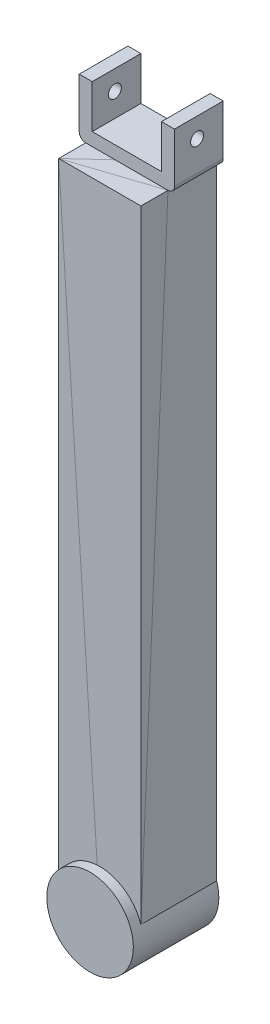
SolidWorks part; units mm, degrees
ref_plane "Front Plane" through (0, 0, 0) normal (0, 0, 1) x (1, 0, 0)
ref_plane "Top Plane" through (0, 0, 0) normal (0, 1, 0) x (1, 0, 0)
ref_plane "Right Plane" through (0, 0, 0) normal (1, 0, 0) x (0, 0, -1)
sketch "Sketch1" plane through (0, 0, 0) normal (0, 1, 0) x (1, 0, 0)
  line L1 (-19, 17.5) -> (19, 17.5)
  line L2 (-19, 17.5) -> (-19, -17.5)
  line L3 (-19, -17.5) -> (19, -17.5)
  line L4 (19, 17.5) -> (19, -17.5)
  line L5 (-19, 17.5) -> (19, -17.5) construction
  line L6 (-19, -17.5) -> (19, 17.5) construction
  point P0 (0, 0)
  dimension "D1" = 35
  dimension "D2" = 38
extrude "Boss-Extrude1" add sketch "Sketch1" against normal blind 295
sketch "Sketch2" plane through (0, 0, 0) normal (0, 0, 1) x (1, 0, 0)
  line L0 (-19, 0) -> (19, 0)
  line L1 (22, 3) -> (22, 26)
  line L2 (-22, 3) -> (-22, 26)
  line L3 (16, 6) -> (16, 26)
  line L4 (-16, 6) -> (16, 6)
  line L5 (-16, 6) -> (-16, 26)
  line L6 (-16, 26) -> (-22, 26)
  line L7 (16, 26) -> (22, 26)
  line L8 (-22, 0) -> (22, 0) construction
  line L9 (-22, 0) -> (-22, 26) construction
  line L10 (22, 0) -> (22, 26) construction
  arc A0 (-19, 0) -> (-22, 3) centre (-19, 3) cw
  arc A1 (19, 0) -> (22, 3) centre (19, 3) ccw
  dimension "D2" = 3
  dimension "D3" = 3
  dimension "D1" = 6
extrude "Boss-Extrude3" add sketch "Sketch2" against normal blind 17.5 and the other way blind 5 separate body
extrude "Boss-Extrude6" add sketch "Sketch1<3>" against normal blind 295
sketch "Sketch1<3>" plane through (0, 0, 0) normal (0, 1, 0) x (1, 0, 0) same geometry as "Sketch1"
ref_plane "Plane2" through (16, 0, 0) normal (-1, 0, 0) x (0, 0, 1)
sketch "Sketch3" plane through (16, 0, 0) normal (-1, 0, 0) x (0, 0, 1)
  circle A0 centre (-5.4606, 16.8963) radius 3
extrude "Cut-Extrude1" cut sketch "Sketch3" against normal up to vertex (6 mm away) up to point (22, 26, -17.5)
mirror "Mirror1" about plane through (0, 0, 0) normal (1, 0, 0) of "Cut-Extrude1"
sketch "Sketch5" plane through (0, 0, 0) normal (0, 0, 1) x (1, 0, 0)
  circle A0 centre (0, -293.7839) radius 20
extrude "Boss-Extrude8" add sketch "Sketch5" along normal blind 22 and the other way up to vertex (17.5 mm away) other way up to point (-19, -295, -17.5)
sketch "Sketch8" plane through (-19, 0, 0) normal (-1, 0, 0) x (0, 0, 1)
  line L0 (5, 0) -> (-17.5, 0) construction
  circle A0 centre (0, -85) radius 5
  dimension "D1" = 85
extrude "Cut-Extrude2" cut sketch "Sketch8" against normal blind 10
ref_point "Point1"
ref_point "Point2"
ref_axis "Axis1" through (16, 16.8963, -5.4606) along (-1, 0, 0)
sketch "Sketch9" plane through (-16, 0, 0) normal (1, 0, 0) x (0, 0, -1)
  line L0 (5.4606, 16.8963) -> (17.5, 16.8963) construction
  line L1 (17.5, 6) -> (17.5, 26) construction
